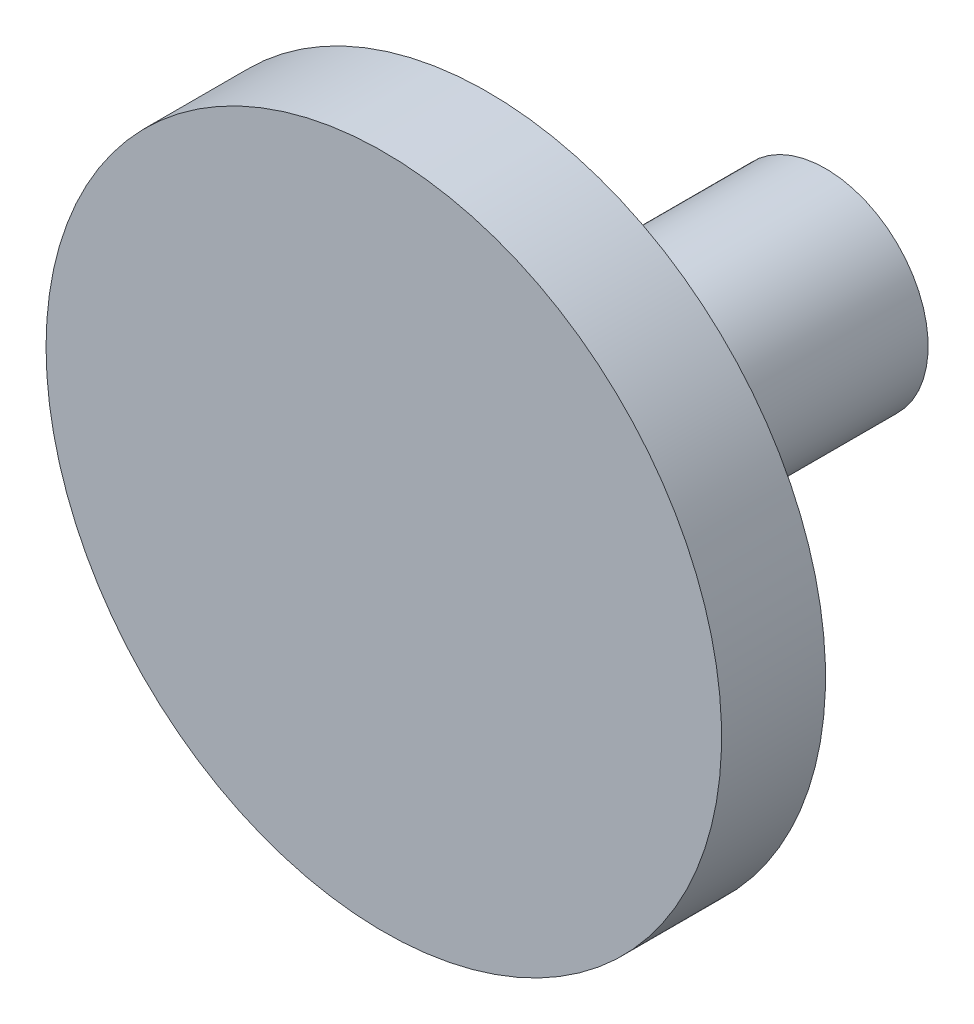
SolidWorks part; units mm, degrees
ref_plane "Alzado" through (0, 0, 0) normal (0, 0, 1) x (1, 0, 0)
ref_plane "Planta" through (0, 0, 0) normal (0, 1, 0) x (1, 0, 0)
ref_plane "Vista lateral" through (0, 0, 0) normal (1, 0, 0) x (0, 0, -1)
sketch "Croquis2" plane through (0, 0, 0) normal (0, 1, 0) x (1, 0, 0)
  line L0 (15.994, 0) -> (-15.994, 0) construction
  line L1 (0, 21.8204) -> (0, -10.2641) construction
  line L2 (-13, 0) -> (-13, 4)
  line L3 (-13, 4) -> (-5.5, 4)
  line L4 (-5.5, 4) -> (-5.5, 7)
  line L5 (-5.5, 7) -> (-3.95, 7)
  line L6 (-3.95, 7) -> (-3.95, 17)
  line L7 (-3.95, 17) -> (0, 17)
  line L8 (-13, 0) -> (0, 0)
  line L9 (0, 17) -> (0, 0)
  dimension "D1" = 13
  dimension "D2" = 4
  dimension "D3" = 3
  dimension "D4" = 10
  dimension "D5" = 3.95
  dimension "D6" = 1.55
revolve "Revolución1" add sketch "Croquis2" angle 360 about L1
